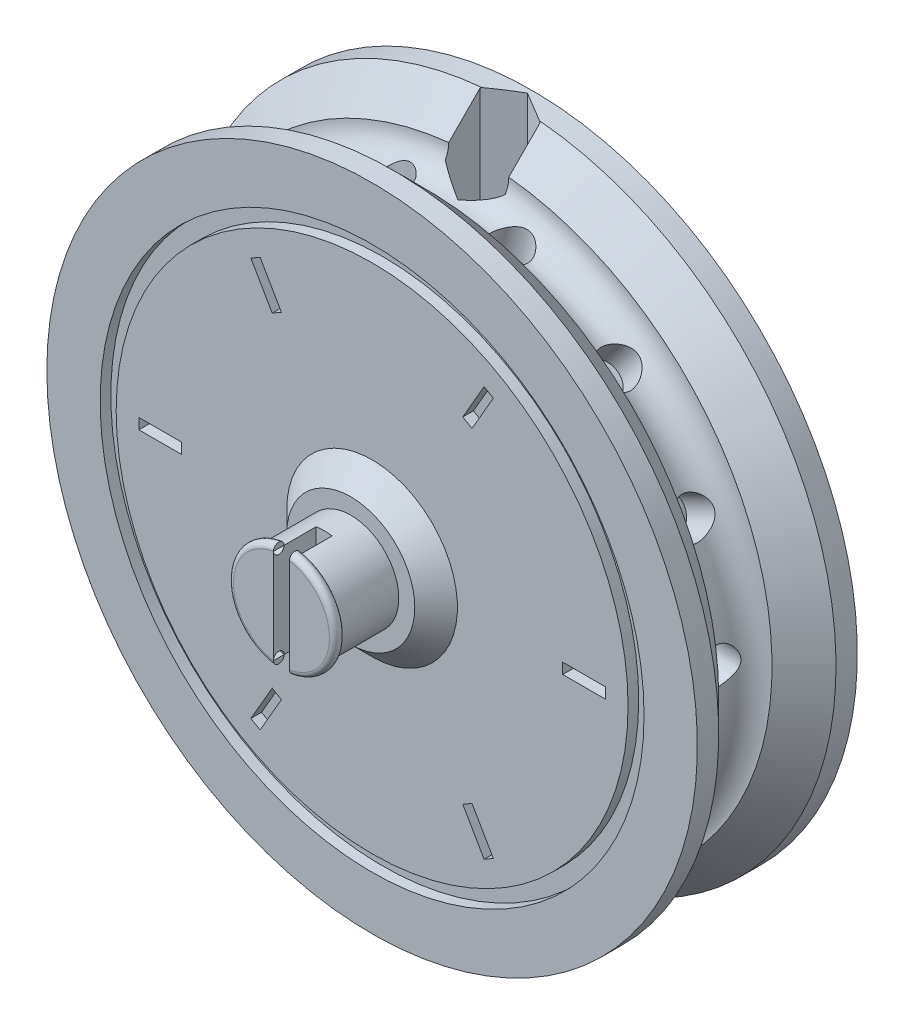
SolidWorks part; units mm, degrees
ref_plane "Alzado" through (0, 0, 0) normal (0, 0, 1) x (1, 0, 0)
ref_plane "Planta" through (0, 0, 0) normal (0, 1, 0) x (1, 0, 0)
ref_plane "Vista lateral" through (0, 0, 0) normal (1, 0, 0) x (0, 0, -1)
ref_plane "Plano1" through (0, 0, -7.7) normal (0, 0, 1) x (1, 0, 0)
sketch "Croquis2" plane through (0, 0, -7.7) normal (0, 0, 1) x (1, 0, 0)
  line L0 (2.829, 4.9) -> (-2.829, 4.9) construction
  line L1 (-3.06, -5.3) -> (3.06, -5.3)
  line L2 (3.06, -5.3) -> (6.1199, 0)
  line L3 (6.1199, 0) -> (3.06, 5.3)
  line L4 (3.06, 5.3) -> (-3.06, 5.3)
  line L5 (-3.06, 5.3) -> (-6.1199, 0)
  line L6 (-6.1199, 0) -> (-3.06, -5.3)
  line L8 (-8.4293, 0) -> (-4.2147, -7.3)
  line L9 (-4.2147, -7.3) -> (4.2147, -7.3)
  line L10 (4.2147, -7.3) -> (8.4293, 0)
  line L11 (8.4293, 0) -> (4.2147, 7.3)
  line L12 (4.2147, 7.3) -> (-4.2147, 7.3)
  line L13 (-4.2147, 7.3) -> (-8.4293, 0)
  circle A0 centre (0, 0) radius 5.3 construction
  circle A1 centre (0, 0) radius 7.3 construction
  dimension "D1" = 0.4
  dimension "D2" = 2
extrude "Saliente-Extruir1" add sketch "Croquis2" along normal up to surface (7.7 mm away)
sketch "Croquis3" plane through (0, -7.3, 0) normal (0, -1, 0) x (1, 0, 0)
  circle A0 centre (0, -4) radius 1.65
  circle A1 centre (0, -4) radius 1.65 construction
extrude "Cortar-Extruir1" cut sketch "Croquis3" against normal through all both and the other way through all
sketch "Croquis4" plane through (0, 0, 0) normal (0, 1, 0) x (1, 0, 0)
  line L0 (0, 7.7) -> (0, -7.3)
  line L1 (-4.2147, 7.7) -> (4.2147, 7.7) construction
  line L2 (0, -7.3) -> (30.5, -7.3)
  line L3 (30.5, -7.3) -> (30.5, -5.3)
  line L4 (30.5, -5.3) -> (27.5, -2.3)
  line L5 (27.5, -2.3) -> (27.5, 2.7) construction
  line L6 (27.5, 2.7) -> (30.5, 5.7)
  line L7 (30.5, 5.7) -> (30.5, 7.7)
  line L8 (30.5, 7.7) -> (0, 7.7)
  line L9 (25, 0.2) -> (0, 0.2) construction
  line L10 (15.25, -7.3) -> (15.25, 0.2) construction
  line L11 (15.25, 0.2) -> (15.25, 7.7) construction
  arc A1 (27.5, 2.7) -> (27.5, -2.3) centre (27.5, 0.2) ccw
  dimension "D1" = 5
  dimension "D2" = 25
  dimension "D3" = 15
  dimension "D4" = 3
  dimension "D5" = 2
revolve "Revolución1" add sketch "Croquis4" angle 360 about L0
sketch "Croquis5" plane through (0, 4.9, 0) normal (0, 1, 0) x (1, 0, 0)
  circle A0 centre (0, 4) radius 2.6
  circle A1 centre (0, 4) radius 1.65 construction
  dimension "D1" = 5.2
  dimension "D2" = 0
extrude "Cortar-Extruir2" cut sketch "Croquis5" against normal through all
sketch "Croquis6" plane through (0, 0, 0) normal (0, 1, 0) x (1, 0, 0)
  line L1 (0, 0.75) -> (2.8146, 2.375)
  line L2 (2.8146, 2.375) -> (2.8146, 5.625)
  line L3 (2.8146, 5.625) -> (0, 7.25)
  line L4 (0, 7.25) -> (-2.8146, 5.625)
  line L5 (-2.8146, 5.625) -> (-2.8146, 2.375)
  line L6 (-2.8146, 2.375) -> (0, 0.75)
  circle A0 centre (0, 4) radius 3.25 construction
  dimension "D1" = 6.5
extrude "Cortar-Extruir3" cut sketch "Croquis6" along normal through all
sketch "Croquis7" plane through (0, 0, 7.3) normal (0, 0, 1) x (1, 0, 0)
  circle A0 centre (0, 0) radius 6
  dimension "D1" = 12
extrude "Saliente-Extruir2" add sketch "Croquis7" along normal blind 2
sketch "Croquis8" plane through (0, 0, 9.3) normal (0, 0, 1) x (1, 0, 0)
  circle A0 centre (0, 0) radius 4.5
  dimension "D1" = 9
extrude "Saliente-Extruir3" add sketch "Croquis8" along normal blind 5.5
chamfer "Chaflán1" distance 2 angle 45 1 edges at (6, 0, 7.3)
sketch "Croquis9" plane through (0, 0, 0) normal (0, 1, 0) x (1, 0, 0)
  line L0 (-4.5, -14.8) -> (-4.5, -15.3) construction
  line L1 (0, -14.8) -> (0, -15.8)
  line L2 (-4.5, -14.8) -> (4.5, -14.8) construction
  line L3 (0, -15.8) -> (-4.5, -15.8)
  line L4 (-4.5, -15.8) -> (-4.5, -14.8)
  line L5 (-4.5, -14.8) -> (0, -14.8)
  circle A0 centre (-4.5, -15.3) radius 0.5
  dimension "D1" = 1
revolve "Revolución2" add sketch "Croquis9" angle 360 about L1 region at (-2.0552, 0, 15.3) region at (-4.7122, 0, 15.3)
sketch "Croquis10" plane through (0, 0, 15.8) normal (0, 0, 1) x (1, 0, 0)
  line L1 (-0.75, 5) -> (0.75, 5)
  line L2 (-0.75, 5) -> (-0.75, -5)
  line L3 (-0.75, -5) -> (0.75, -5)
  line L4 (0.75, 5) -> (0.75, -5)
  line L5 (-0.75, 5) -> (0.75, -5) construction
  line L6 (-0.75, -5) -> (0.75, 5) construction
  circle A0 centre (0, 0) radius 5 construction
  point P0 (0, 0)
  dimension "D1" = 1.5
extrude "Cortar-Extruir6" cut sketch "Croquis10" against normal blind 4
sketch "Croquis12" plane through (0, 0, -7.7) normal (0, 0, -1) x (-1, 0, 0)
  line L1 (6.1199, 0) -> (3.06, 5.3)
  line L2 (3.06, 5.3) -> (-3.06, 5.3)
  line L3 (-3.06, 5.3) -> (-6.1199, 0)
  line L4 (-6.1199, 0) -> (-3.06, -5.3)
  line L5 (-3.06, -5.3) -> (3.06, -5.3)
  line L6 (3.06, -5.3) -> (6.1199, 0)
  circle A0 centre (0, 0) radius 5.3 construction
extrude "Cortar-Extruir7" cut sketch "Croquis12" against normal blind 8
sketch "Croquis13" plane through (0, 0, 0) normal (1, 0, 0) x (0, 0, -1)
  line L0 (0.2, 25) -> (0.2, -25) construction
  line L1 (0.2, 25) -> (-2.3, 25) construction
  line L2 (-2.3, 25) -> (0.2, 25) construction
  line L3 (0.2, 25) -> (2.7, 25) construction
  line L4 (2.7, 27.3556) -> (2.7, -27.4077) construction
  line L5 (-2.3, 27.5) -> (-2.3, -27.5) construction
  arc A0 (-2.3, 27.5) -> (0.75, 25.0613) centre (0.2, 27.5) ccw construction
  arc A1 (1.4, -25.3069) -> (-2.3, -27.5) centre (0.2, -27.5) ccw construction
sketch "Croquis14" plane through (0, 0, 7.3) normal (0, 0, 1) x (1, 0, 0)
  line L0 (0, 25) -> (0, -25) construction
  line L1 (0, 25) -> (0, -25) construction
  line L3 (25, 25) -> (-25, 25)
  line L4 (25, 25) -> (25, -25)
  line L5 (25, -25) -> (-25, -25)
  line L6 (-25, 25) -> (-25, -25)
  line L7 (25, 25) -> (-25, -25) construction
  line L8 (25, -25) -> (-25, 25) construction
  circle A0 centre (0, 0) radius 25
sketch "Croquis15" plane through (0, 0, 7.3) normal (0, 0, 1) x (1, 0, 0)
  circle A0 centre (0, 0) radius 24
  circle A1 centre (0, 0) radius 25.5
  circle A2 centre (0, 0) radius 30.5 construction
  dimension "D1" = 5
  dimension "D2" = 1.5
extrude "Cortar-Extruir8" cut sketch "Croquis15" against normal blind 1
ref_plane "Plano2" through (30.5, 0, 0) normal (1, 0, 0) x (0, 0, -1)
sketch "Croquis16" plane through (30.5, 0, 0) normal (1, 0, 0) x (0, 0, -1)
  circle A0 centre (0, 0) radius 1.75
  dimension "D1" = 3.5
extrude "Cortar-Extruir10" cut sketch "Croquis16" against normal blind 8
pattern_circular "MatrizC1" count 14 over 360 about axis through (0, 0, -7.7) along (0, 0, -1) of "Cortar-Extruir10"
sketch "Croquis17" plane through (0, 0, 7.3) normal (0, 0, 1) x (1, 0, 0)
  line L0 (19.8705, 0) -> (0, 0) construction
  line L1 (21.8705, 0.5) -> (17.8705, 0.5)
  line L2 (21.8705, 0.5) -> (21.8705, -0.5)
  line L3 (21.8705, -0.5) -> (17.8705, -0.5)
  line L4 (17.8705, 0.5) -> (17.8705, -0.5)
  line L5 (21.8705, 0.5) -> (17.8705, -0.5) construction
  line L6 (21.8705, -0.5) -> (17.8705, 0.5) construction
  point P0 (19.8705, 0)
  dimension "D2" = 4
  dimension "D1" = 1
extrude "Cortar-Extruir11" cut sketch "Croquis17" against normal blind 1
pattern_circular "MatrizC2" count 6 over 360 about axis through (0, 0, 7.3) along (0, 0, -1) of "Cortar-Extruir11"
